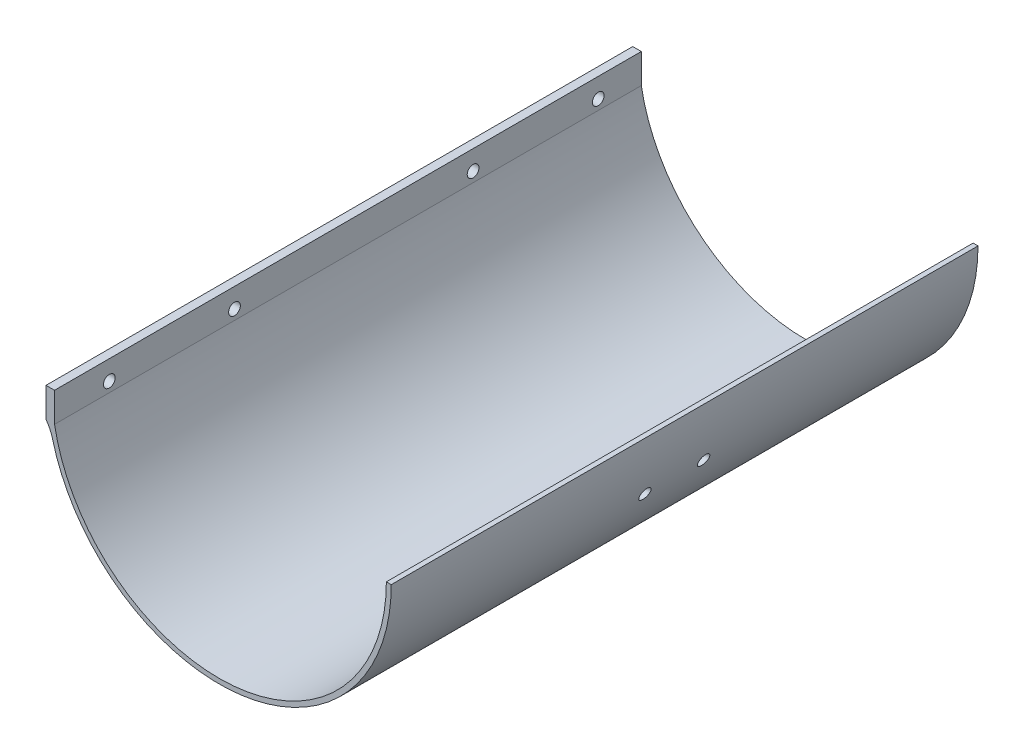
SolidWorks part; units mm, degrees
ref_plane "Front Plane" through (0, 0, 0) normal (0, 0, 1) x (1, 0, 0)
ref_plane "Top Plane" through (0, 0, 0) normal (0, 1, 0) x (1, 0, 0)
ref_plane "Right Plane" through (0, 0, 0) normal (1, 0, 0) x (0, 0, -1)
sketch "Sketch1" plane through (0, 0, 0) normal (0, 0, 1) x (1, 0, 0)
  line L0 (-44, 0) -> (-42.75, 0)
  line L1 (42.75, 0) -> (44, 0)
  arc A0 (-44, 0) -> (44, 0) centre (0, 0) ccw
  arc A1 (-42.75, 0) -> (42.75, 0) centre (0, 0) ccw
  dimension "D1" = 88
  dimension "D2" = 85.5
extrude "Boss-Extrude1" add sketch "Sketch1" along normal blind 150
sketch "Sketch2" plane through (0, 0, 0) normal (1, 0, 0) x (0, 0, -1)
  line L2 (-150, 0) -> (0, 0) construction
  line L3 (-150, 0) -> (-150, -44) construction
  circle A0 centre (-136, -5) radius 1.5
  circle A1 centre (-104, -5) radius 1.5
  circle A2 centre (-43, -5) radius 1.5
  circle A3 centre (-11, -5) radius 1.5
  dimension "D1" = 3
  dimension "D2" = 3
  dimension "D3" = 3
  dimension "D4" = 3
  dimension "D5" = 32
  dimension "D6" = 32
  dimension "D7" = 61
  dimension "D8" = 14
  dimension "D10" = 5
extrude "Cut-Extrude1" cut sketch "Sketch2" against normal up to surface (43.715 mm away) up to face at (0, -22, 75)
ref_plane "Plane1" through (0, 0, 72) normal (0, 0, -1) x (-1, 0, 0)
sketch "Sketch4" plane through (0, 0, 72) normal (0, 0, -1) x (-1, 0, 0)
  line L0 (-42.1884, 12.4954) -> (-40.8831, 12.4954)
  line L1 (-44, 0) -> (-42.75, 0)
  arc A0 (-40.8831, 12.4954) -> (-42.75, 0) centre (0, 0) ccw
  arc A1 (-42.1884, 12.4954) -> (-44, 0) centre (0, 0) ccw
  dimension "D1" = 88
  dimension "D2" = 85.5
extrude "Boss-Extrude2" add sketch "Sketch4" along normal blind 7.5 and the other way blind 7.5
sketch "Sketch5" plane through (0, 0, 150) normal (0, 0, 1) x (1, 0, 0)
  line L5 (-44, 0) -> (-44, -7.5543)
  line L6 (-44, -7.5543) -> (-42.7628, -7.5543)
  line L7 (-42.7628, -7.5543) -> (-42.7628, 0)
  line L8 (-42.75, 0) -> (-44, 0) construction
  line L9 (-42.7628, 0) -> (-44, 0)
extrude "Cut-Extrude2" cut sketch "Sketch5" against normal up to surface (150 mm away) up to face at (0, -21.6875, 0)
sketch "Sketch6" plane through (-42.7628, 0, 0) normal (-1, 0, 0) x (0, 0, 1)
  line L1 (0, -7.5543) -> (150, -7.5543)
  line L2 (0, -7.5543) -> (0, 0)
  line L3 (0, 0) -> (150, 0)
  line L4 (150, -7.5543) -> (150, 0)
  circle A0 centre (11, -5) radius 1.5
  circle A1 centre (43, -5) radius 1.5
  circle A2 centre (104, -5) radius 1.5
  circle A3 centre (136, -5) radius 1.5
  circle M5 centre (43, -5) radius 1.5
  circle M6 centre (136, -5) radius 1.5
  line M7 (0, 0) -> (0, -7.5543)
  line M8 (0, -7.5543) -> (150, -7.5543)
  line M9 (150, -7.5543) -> (150, 0)
  line M10 (150, 0) -> (0, 0)
  circle M11 centre (104, -5) radius 1.5
  circle M12 centre (11, -5) radius 1.5
extrude "Boss-Extrude3" add sketch "Sketch6" along normal blind 0.5 contours M10 M7 M8 M9 M6 M11 M12 M5 region at (-42.7628, -3.7459, 75.0384)
sketch "Sketch7" plane through (0, 0, 150) normal (0, 0, 1) x (1, 0, 0)
  line L0 (3.1936, -47.2716) -> (4.2473, -46.1824)
  line L2 (2.6526, -44.3202) -> (7.0646, -42.9225)
  line L3 (2.6526, -44.3202) -> (-0.0812, -45.0066)
  line L4 (-2.6526, -44.3202) -> (-7.0646, -42.9225)
  arc A1 (-0.0812, -45.0066) -> (3.1936, -47.2716) centre (-0.0812, -48.5066) ccw
  arc A2 (-2.6526, -44.3202) -> (4.2473, -46.1824) centre (-0.0812, -48.5066) ccw
  arc A3 (-7.0646, -42.9225) -> (7.0646, -42.9225) centre (0, 0) ccw
  dimension "D1" = 43.5
  dimension "D2" = 7
extrude "Boss-Extrude4" add sketch "Sketch7" against normal blind 80
fillet "Fillet3" radius 0.5 1 edges at (4.2473, -46.1824, 110)
sketch "Sketch9" plane through (0, 0, 0) normal (1, 0, 0) x (0, 0, -1)
  line L0 (-79.5, 12.4954) -> (-79.5, 0) construction
  line L1 (-78, 8.4954) -> (-66, 8.4954)
  line L2 (-78, 8.4954) -> (-78, 2.4954)
  line L3 (-78, 2.4954) -> (-66, 2.4954)
  line L4 (-66, 8.4954) -> (-66, 2.4954)
  line L5 (-79.5, 12.4954) -> (-64.5, 12.4954) construction
  dimension "D1" = 12
  dimension "D2" = 6
  dimension "D3" = 1.5
  dimension "D4" = 4
extrude "Cut-Extrude4" cut sketch "Sketch9" along normal up to surface (43.1721 mm away) up to face at (15.0324, -18.3013, 85.6667)
sketch "Sketch11" plane through (0, 0, 150) normal (0, 0, 1) x (1, 0, 0)
  line L1 (6.0382, -53.7585) -> (4.3409, -43.7853)
  line L2 (6.0382, -53.7585) -> (2.0015, -51.3196)
  line L3 (-6.6638, -46.7537) -> (-4.3409, -43.7853)
  line L4 (2.6526, -44.3202) -> (4.3409, -43.7853) construction
  arc A1 (-6.6638, -46.7537) -> (6.0382, -53.7585) centre (2.0015, -46.0596) ccw
  arc A2 (-4.3409, -43.7853) -> (4.3409, -43.7853) centre (0, 0) ccw
  arc A3 (-0.0812, -45.0066) -> (3.1936, -47.2716) centre (-0.0812, -48.5066) ccw construction
  arc A4 (4.3409, -43.7853) -> (44, 0) centre (0, 0) ccw construction
  dimension "D1" = 44
extrude "Cut-Extrude5" cut sketch "Sketch11" against normal blind 67 contours A1 L3 A2 L1
sketch "Sketch12" plane through (0, 0, 0) normal (0, 0, -1) x (-1, 0, 0)
  line L2 (42.75, 0) -> (42.75, -7.5543)
  line L6 (42.75, -7.5543) -> (41.523, -7.5543)
  line L7 (41.523, -7.5543) -> (42.75, 0)
extrude "Cut-Extrude6" cut sketch "Sketch12" against normal up to surface (150 mm away) up to face at (-13.7346, -16.3196, 150)
sketch "Sketch14" plane through (-43.2628, 0, 0) normal (-1, 0, 0) x (0, 0, 1)
  line L0 (0, -7.5543) -> (150, -7.5543) construction
  line L1 (0, 0) -> (150, 0)
  line L2 (0, 0) -> (0, -7.5543)
  line L3 (0, -7.5543) -> (150, -7.5543)
  line L4 (150, 0) -> (150, -7.5543)
  line L5 (150, -7.5543) -> (150, 0) construction
  circle A0 centre (11, -5) radius 1.5
  circle A1 centre (43, -5) radius 1.5
  circle A2 centre (104, -5) radius 1.5
  circle A3 centre (136, -5) radius 1.5
extrude "Boss-Extrude5" add sketch "Sketch14" along normal blind 1 and the other way blind 1.5
sketch "Sketch17" plane through (0, -7.5543, 0) normal (0, -1, 0) x (1, 0, 0)
  line L1 (-42.0773, 150) -> (-41.7628, 150)
  line L2 (-42.0773, 150) -> (-42.0773, 0)
  line L3 (-42.0773, 0) -> (-41.7628, 0)
  line L4 (-41.7628, 150) -> (-41.7628, 0)
extrude "Cut-Extrude8" cut sketch "Sketch17" against normal up to surface (7.5543 mm away) up to face at (-43.0128, 0, 75)
fillet "Fillet4" radius 10 1 edges at (-43.3467, -7.5543, 75)
sketch "Sketch18" plane through (0, 0, 79.5) normal (0, 0, 1) x (1, 0, 0)
  line L1 (40.1344, 0) -> (45.8139, 0)
  line L2 (40.1344, 0) -> (40.1344, 15.0548)
  line L3 (40.1344, 15.0548) -> (45.8139, 15.0548)
  line L4 (45.8139, 0) -> (45.8139, 15.0548)
extrude "Cut-Extrude9" cut sketch "Sketch18" against normal up to surface (15 mm away) up to face at (42.6841, 6.2814, 64.5)
sketch "Sketch19" plane through (-42.0773, 0, 0) normal (1, 0, 0) x (0, 0, -1)
  line L0 (-75, 0) -> (-75, -20.7313) construction
  line L1 (-150, 0) -> (0, 0) construction
  circle A0 centre (-82.5, -15) radius 1.5
  circle A1 centre (-67.5, -15) radius 1.5
  dimension "D1" = 3
  dimension "D2" = 3
  dimension "D3" = 15
  dimension "D4" = 7.5
  dimension "D5" = 15
extrude "Cut-Extrude10" cut sketch "Sketch19" along normal up to surface (63.4415 mm away) from offset 20 up to face at (3.1311, -24.5812, 75)
sketch "Sketch20" plane through (0, 0, 70) normal (0, 0, -1) x (-1, 0, 0)
  line L0 (4.2376, -51.1264) -> (9.3647, -42.9919)
  line L1 (2.6526, -44.3202) -> (4.3409, -43.7853)
  arc A0 (4.2376, -51.1264) -> (2.6526, -44.3202) centre (0.0812, -48.5066) ccw
  arc A3 (-44, 0) -> (42.595, -11.0303) centre (0, 0) ccw construction
  arc A4 (4.3409, -43.7853) -> (9.3647, -42.9919) centre (0, 0) ccw
  arc A5 (-4.5622, -46.9012) -> (2.6526, -44.3202) centre (0.0812, -48.5066) ccw construction
extrude "Boss-Extrude6" add sketch "Sketch20" against normal up to surface (13 mm away) up to face at (0.6422, -46.8572, 83)
